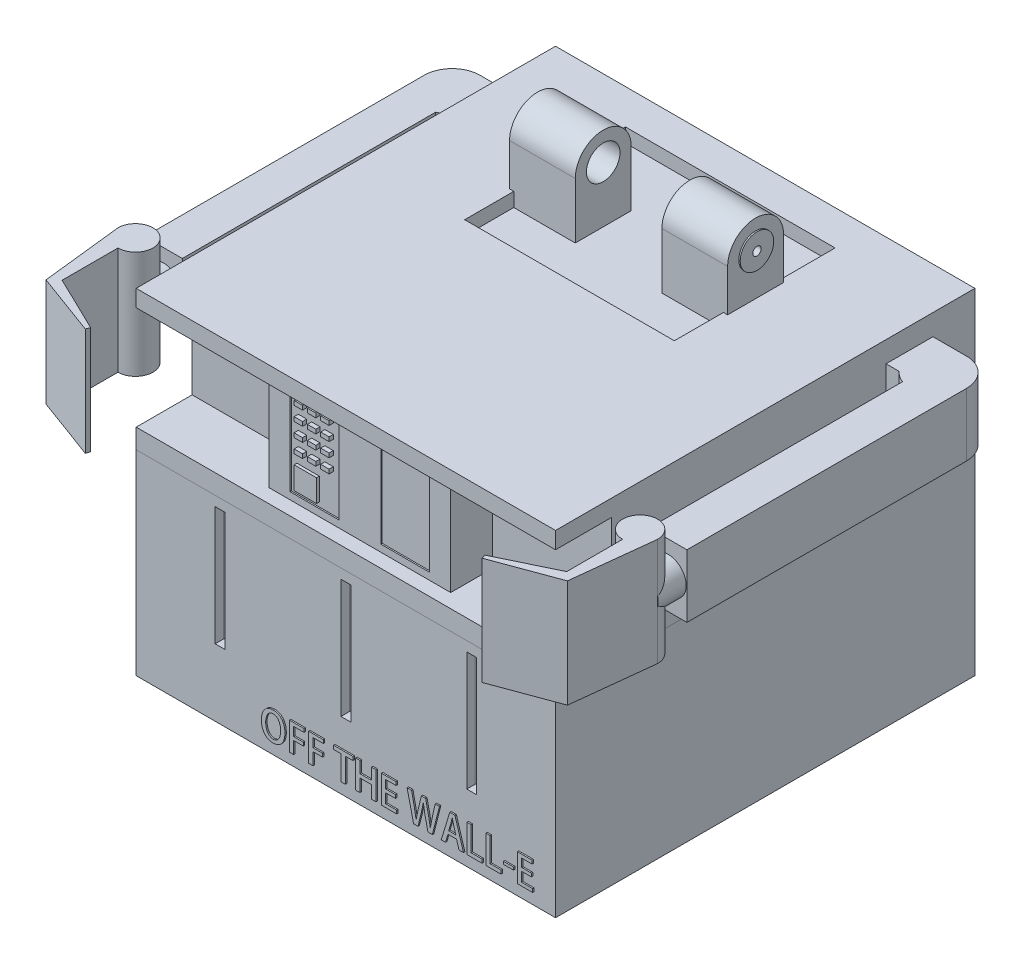
SolidWorks part; units mm, degrees
material "Polyethylene Cross-Linked"
ref_plane "Front" through (0, 0, 0) normal (0, 0, 1) x (1, 0, 0)
ref_plane "Top" through (0, 0, 0) normal (0, 1, 0) x (1, 0, 0)
ref_plane "Right" through (0, 0, 0) normal (1, 0, 0) x (0, 0, -1)
sketch "Base" plane through (0, 0, 0) normal (0, 1, 0) x (1, 0, 0)
  line L1 (-7.5, -7.5) -> (7.5, -7.5)
  line L2 (-7.5, -7.5) -> (-7.5, 7.5)
  line L3 (-7.5, 7.5) -> (7.5, 7.5)
  line L4 (7.5, -7.5) -> (7.5, 7.5)
  line L5 (-7.5, -7.5) -> (7.5, 7.5) construction
  line L6 (-7.5, 7.5) -> (7.5, -7.5) construction
  point P0 (0, 0)
  dimension "D1" = 15
  dimension "D2" = 15
extrude "Bottom base" add sketch "Base" along normal blind 7
sketch "Base2" plane through (0, 7, 0) normal (0, 1, 0) x (1, 0, 0)
  line L1 (-7.5, -7.5) -> (7.5, -7.5)
  line L2 (-7.5, -7.5) -> (-7.5, 7.5)
  line L3 (-7.5, 7.5) -> (7.5, 7.5)
  line L4 (7.5, -7.5) -> (7.5, 7.5)
  line L5 (-7.5, -7.5) -> (7.5, 7.5) construction
  line L6 (-7.5, 7.5) -> (7.5, -7.5) construction
  point P0 (0, 0)
extrude "Top base" add sketch "Base2" along normal blind 5 separate body
sketch "Sketch3" plane through (0, 0, 7.5) normal (0, 0, 1) x (1, 0, 0)
  line L7 (-7.5, 12) -> (-7.5, 7) construction
  line L8 (-7.5, 11.4) -> (7.5, 11.4)
  line L9 (-7.5, 11.4) -> (-7.5, 7.7)
  line L10 (-7.5, 7.7) -> (7.5, 7.7)
  line L11 (7.5, 11.4) -> (7.5, 7.7)
  line L12 (7.5, 12) -> (7.5, 7) construction
  line L13 (-7.5, 7) -> (7.5, 7) construction
  line L14 (-7.5, 12) -> (7.5, 12) construction
  dimension "D1" = 0.7
  dimension "D2" = 0.6
extrude "Top cut" cut sketch "Sketch3" against normal blind 2
sketch "Sketch4" plane through (0, 0, 5.5) normal (0, 0, 1) x (1, 0, 0)
  line L0 (7.5, 11.4) -> (-7.5, 11.4) construction
  line L1 (-3.25, 11.4) -> (3.25, 11.4)
  line L2 (-3.25, 11.4) -> (-3.25, 7.7)
  line L3 (-3.25, 7.7) -> (3.25, 7.7)
  line L4 (3.25, 11.4) -> (3.25, 7.7)
  line L5 (-7.5, 7.7) -> (7.5, 7.7) construction
  line L6 (-7.5, 11.4) -> (-7.5, 7.7) construction
  line L7 (7.5, 7.7) -> (7.5, 11.4) construction
  dimension "D1" = 4.25
  dimension "D2" = 4.25
extrude "Big button plate" add sketch "Sketch4" along normal blind 1.5
sketch "Sketch6" plane through (0, 0, 7) normal (0, 0, 1) x (1, 0, 0)
  line L0 (0, -55) -> (0, 55) construction
  line L1 (-2.5, 11.15) -> (-0.75, 11.15)
  line L2 (-2.5, 11.15) -> (-2.5, 7.95)
  line L3 (-2.5, 7.95) -> (-0.75, 7.95)
  line L4 (-0.75, 11.15) -> (-0.75, 7.95)
  line L5 (2.5, 7.95) -> (0.75, 7.95)
  line L6 (0.75, 11.15) -> (0.75, 7.95)
  line L7 (2.5, 11.15) -> (0.75, 11.15)
  line L8 (2.5, 11.15) -> (2.5, 7.95)
  line L9 (3.25, 11.4) -> (-3.25, 11.4) construction
  line L10 (-7.5, 7.7) -> (7.5, 7.7) construction
  line L11 (-1.775, 10.9491) -> (-1.775, 10.7991)
  line L12 (-3.25, 11.4) -> (-3.25, 7.7) construction
  line L13 (-2.5, 9.1045) -> (-0.75, 9.1045) construction
  line L14 (-1.775, 10.9491) -> (-1.475, 10.9491)
  line L15 (-2.25, 10.9491) -> (-1.95, 10.9491)
  line L16 (-2.25, 10.9491) -> (-2.25, 10.7991)
  line L17 (-2.25, 10.7991) -> (-1.95, 10.7991)
  line L18 (-1.95, 10.9491) -> (-1.95, 10.7991)
  line L19 (-1.475, 10.9491) -> (-1.475, 10.7991)
  line L20 (-1.775, 10.7991) -> (-1.475, 10.7991)
  line L21 (-1.3, 10.9491) -> (-1.3, 10.7991)
  line L22 (-1.3, 10.9491) -> (-1, 10.9491)
  line L23 (-1, 10.9491) -> (-1, 10.7991)
  line L24 (-1.3, 10.7991) -> (-1, 10.7991)
  line L25 (-2.25, 10.4491) -> (-2.25, 10.2991)
  line L26 (-2.25, 10.4491) -> (-1.95, 10.4491)
  line L27 (-1.95, 10.4491) -> (-1.95, 10.2991)
  line L28 (-2.25, 10.2991) -> (-1.95, 10.2991)
  line L29 (-1.775, 10.4491) -> (-1.775, 10.2991)
  line L30 (-1.775, 10.2991) -> (-1.475, 10.2991)
  line L31 (-1.475, 10.4491) -> (-1.475, 10.2991)
  line L32 (-1.775, 10.4491) -> (-1.475, 10.4491)
  line L33 (-1.3, 10.4491) -> (-1.3, 10.2991)
  line L34 (-1.3, 10.2991) -> (-1, 10.2991)
  line L35 (-1, 10.4491) -> (-1, 10.2991)
  line L36 (-1.3, 10.4491) -> (-1, 10.4491)
  line L37 (-2.25, 9.9491) -> (-2.25, 9.7991)
  line L38 (-2.25, 9.9491) -> (-1.95, 9.9491)
  line L39 (-1.95, 9.9491) -> (-1.95, 9.7991)
  line L40 (-2.25, 9.7991) -> (-1.95, 9.7991)
  line L41 (-1.775, 9.9491) -> (-1.775, 9.7991)
  line L42 (-1.775, 9.7991) -> (-1.475, 9.7991)
  line L43 (-1.475, 9.9491) -> (-1.475, 9.7991)
  line L44 (-1.775, 9.9491) -> (-1.475, 9.9491)
  line L45 (-1.3, 9.9491) -> (-1.3, 9.7991)
  line L46 (-1.3, 9.7991) -> (-1, 9.7991)
  line L47 (-1, 9.9491) -> (-1, 9.7991)
  line L48 (-1.3, 9.9491) -> (-1, 9.9491)
  line L49 (-2.25, 9.4491) -> (-2.25, 9.2991)
  line L50 (-2.25, 9.4491) -> (-1.95, 9.4491)
  line L51 (-1.95, 9.4491) -> (-1.95, 9.2991)
  line L52 (-2.25, 9.2991) -> (-1.95, 9.2991)
  line L53 (-1.775, 9.4491) -> (-1.775, 9.2991)
  line L54 (-1.775, 9.2991) -> (-1.475, 9.2991)
  line L55 (-1.475, 9.4491) -> (-1.475, 9.2991)
  line L56 (-1.775, 9.4491) -> (-1.475, 9.4491)
  line L57 (-1.3, 9.4491) -> (-1.3, 9.2991)
  line L58 (-1.3, 9.2991) -> (-1, 9.2991)
  line L59 (-1, 9.4491) -> (-1, 9.2991)
  line L60 (-1.3, 9.4491) -> (-1, 9.4491)
  point P32 (-1.875, 11.6241)
  dimension "D1" = 0.25
  dimension "D2" = 0.25
  dimension "D3" = 0.75
  dimension "D4" = 0.75
  dimension "D5" = 0.25
  dimension "D6" = 0.3
  dimension "D7" = 0.15
  dimension "D8" = 0.2009
  dimension "D10" = 0.25
  dimension "D9" = 3
  dimension "D11" = 4
extrude "3x4 buttons" add sketch "Sketch6" along normal blind 0.1 contours L37 L40 L39 L38 | L25 L28 L27 L26 | L16 L15 L18 L17 | L11 L20 L19 L14 | L21 L24 L23 L22 | L33 L34 L35 L36 | L29 L30 L31 L32 | L41 L42 L43 L44 | L45 L46 L47 L48 | L57 L58 L59 L60 | L53 L54 L55 L56 | L49 L52 L51 L50
sketch "Sketch9" plane through (0, 0, 7) normal (0, 0, 1) x (1, 0, 0)
  line L0 (-2.25, 9.4491) -> (-2.25, 9.2991) construction
  line L1 (-2.25, 8.9573) -> (-1.45, 8.9573)
  line L2 (-2.25, 8.9573) -> (-2.25, 8.1573)
  line L3 (-2.25, 8.1573) -> (-1.45, 8.1573)
  line L4 (-1.45, 8.9573) -> (-1.45, 8.1573)
  dimension "D1" = 0.8
  dimension "D2" = 0.8
  dimension "D3" = 0
extrude "Big square button" add sketch "Sketch9" along normal blind 0.1
extrude "phone" cut sketch "Sketch6<6>" against normal blind 0.05
sketch "Sketch6<6>" plane through (0, 0, 7) normal (0, 0, 1) x (1, 0, 0) same geometry as "Sketch6"
sketch "Sketch14" plane through (0, 0, 7.5) normal (0, 0, 1) x (1, 0, 0)
  line L0 (0, -55) -> (0, 55) construction
  line L1 (-0.175, 2.4) -> (0.175, 2.4)
  line L2 (-0.175, 2.4) -> (-0.175, 6.65)
  line L3 (-0.175, 6.65) -> (0.175, 6.65)
  line L4 (0.175, 2.4) -> (0.175, 6.65)
  line L5 (-0.175, 2.4) -> (0.175, 6.65) construction
  line L6 (-0.175, 6.65) -> (0.175, 2.4) construction
  line L7 (-7.5, 7) -> (7.5, 7) construction
  line L8 (4.325, 2.4) -> (4.325, 6.65)
  line L9 (4.325, 2.4) -> (4.675, 2.4)
  line L10 (4.675, 2.4) -> (4.675, 6.65)
  line L11 (4.325, 6.65) -> (4.675, 6.65)
  line L12 (-0.175, 2.4) -> (-0.175, 6.65)
  line L13 (-0.175, 2.4) -> (0.175, 2.4)
  line L14 (0.175, 2.4) -> (0.175, 6.65)
  line L15 (-0.175, 6.65) -> (0.175, 6.65)
  line L16 (-4.675, 2.4) -> (-4.675, 6.65)
  line L17 (-4.675, 2.4) -> (-4.325, 2.4)
  line L18 (-4.325, 2.4) -> (-4.325, 6.65)
  line L19 (-4.675, 6.65) -> (-4.325, 6.65)
  point P0 (0, 4.525)
  dimension "D1" = 0.35
  dimension "D2" = 4.25
  dimension "D3" = 0.35
  dimension "D4" = 2
  dimension "D5" = 2
extrude "3 bottom slots" cut sketch "Sketch14" against normal blind 0.35 contours L19 L16 L17 L18 | L11 L8 L9 L10 | L4 L3 L2 L1 region at (4.5, 4.525, 7.5) region at (-4.5, 4.525, 7.5)
fillet "Fillet1" radius 0.05 12 edges at (-0.175, 4.525, 7.15) (-4.675, 4.525, 7.15) (4.675, 4.525, 7.15) (4.5, 6.65, 7.15) (0.175, 4.525, 7.15) (0, 6.65, 7.15) (4.325, 4.525, 7.15) (4.5, 2.4, 7.15) (0, 2.4, 7.15) (-4.5, 2.4, 7.15) (-4.5, 6.65, 7.15) (-4.325, 4.525, 7.15)
sketch "Sketch15" plane through (0, 12, 0) normal (0, 1, 0) x (1, 0, 0)
  line L0 (0, -6.6) -> (0, 6.6) construction
  line L1 (-3.75, 0.5) -> (3.75, 0.5)
  line L2 (-3.75, 0.5) -> (-3.75, 6.25)
  line L3 (-3.75, 6.25) -> (3.75, 6.25)
  line L4 (3.75, 0.5) -> (3.75, 6.25)
  line L5 (-3.75, 0.5) -> (3.75, 6.25) construction
  line L6 (-3.75, 6.25) -> (3.75, 0.5) construction
  line L7 (7.5, 7.5) -> (-7.5, 7.5) construction
  line L8 (-6.6, 0) -> (6.6, 0) construction
  line L9 (-7.5, 7.5) -> (-7.5, -7.5) construction
  point P0 (0, 3.375)
  dimension "D1" = 1.25
  dimension "D2" = 0.5
  dimension "D3" = 3.75
extrude "Top extrude cut" cut sketch "Sketch15" against normal blind 0.5
sketch "Sketch18" plane through (-3.75, 0, 0) normal (1, 0, 0) x (0, 0, -1)
  line L0 (2.2556, 11.5) -> (4.2556, 11.5)
  line L1 (6.25, 11.5) -> (0.5, 11.5) construction
  line L3 (2.2556, 11.5) -> (2.2556, 13.5)
  line L4 (4.2556, 11.5) -> (4.2556, 13.5)
  arc A0 (2.2556, 13.5) -> (4.2556, 13.5) centre (3.2556, 13.5) cw
  circle A1 centre (3.2556, 13.5) radius 0.6
  circle A2 centre (3.2556, 13.5) radius 0.15
  line M6 (6.25, 12) -> (0.5, 12)
  line M8 (0.5, 11.5) -> (6.25, 11.5)
  dimension "D5" = 0.3
  dimension "D1" = 2
  dimension "D2" = 2
  dimension "D3" = 2
  dimension "D4" = 0.4
sketch "Sketch19" plane through (3.75, 0, 0) normal (-1, 0, 0) x (0, 0, 1)
  line L0 (-4.2556, 13.5) -> (-4.2556, 11.5)
  line L1 (-4.2556, 11.5) -> (-2.2556, 11.5)
  line L2 (-2.2556, 11.5) -> (-2.2556, 13.5)
  arc A0 (-4.2556, 13.5) -> (-2.2556, 13.5) centre (-3.2556, 13.5) cw
  circle A1 centre (-3.2556, 13.5) radius 0.6
  circle A2 centre (-3.2556, 13.5) radius 0.15
  line M1 (-0.5, 12) -> (-6.25, 12)
  line M3 (-6.25, 11.5) -> (-0.5, 11.5)
extrude "Right head holder 1" add sketch "Sketch19" along normal blind 2.2 and the other way blind 0.15 contours A0 L0 L2 A1 M1 | L2 L0 M3 M1 region at (3.75, 14.468, -3.2556) region at (3.75, 11.75, -3.2556)
extrude "Right head holder 2" add sketch "Sketch19<3>" against normal blind 0.2 and the other way blind 0.35 contours A1 A2 region at (3.75, 13.5, -3.8386)
sketch "Sketch19<3>" plane through (3.75, 0, 0) normal (-1, 0, 0) x (0, 0, 1) same geometry as "Sketch19"
extrude "Left head holder 1" add sketch "Sketch18" along normal blind 2.2 and the other way blind 0.15 contours L4 L3 M8 M6 | A0 L3 L4 A1 M6 region at (-3.75, 11.75, -3.2556) region at (-3.75, 12.75, -2.2876)
extrude "Left head holder 2" add sketch "Sketch18<3>" along normal blind 0.35 and the other way blind 0.2 contours A1 A2 region at (-3.75, 13.5, -2.6726)
sketch "Sketch18<3>" plane through (-3.75, 0, 0) normal (1, 0, 0) x (0, 0, -1) same geometry as "Sketch18"
ref_plane "Plane9" through (0, 9, 0) normal (0, 1, 0) x (1, 0, 0)
sketch "Sketch21" plane through (0, 9, 0) normal (0, 1, 0) x (1, 0, 0)
  line L0 (7.9641, 4.3229) -> (7.5, 4.3229)
  line L1 (7.5, 6) -> (7.5, 4.3229)
  line L5 (0, -6.6) -> (0, 6.6) construction
  line L12 (8.7, 6) -> (7.5, 6)
  line L17 (9.7, 5) -> (8.35, 5)
  line L18 (9.7, 5) -> (9.7, -5)
  line L19 (9.7, -5) -> (8.35, -5)
  line L20 (8.35, 5) -> (8.35, -5)
  line L21 (7.5, -7.5) -> (7.5, 7.5) construction
  line L22 (-8.7, 6) -> (-7.5, 6)
  line L23 (-7.5, 6) -> (-7.5, 4.3229)
  line L24 (-7.9641, 4.3229) -> (-7.5, 4.3229)
  line L25 (-9.7, -5) -> (-8.35, -5)
  line L26 (-8.35, 5) -> (-8.35, -5)
  line L27 (-9.7, 5) -> (-8.35, 5)
  line L28 (-9.7, 5) -> (-9.7, -5)
  circle A6 centre (8.7, 5) radius 1
  arc A7 (8.7, 6) -> (7.9641, 4.3229) centre (8.7, 5) ccw
  arc A8 (-8.7, 6) -> (-7.9641, 4.3229) centre (-8.7, 5) cw
  circle A9 centre (-8.7, 5) radius 1
  point P1 (8.7, 5)
  point P19 (7.9641, 4.3229)
  dimension "D1" = 2
  dimension "D2" = 1.35
  dimension "D3" = 10
  dimension "D4" = 1.2
extrude "arms" add sketch "Sketch21" along normal blind 2.25 contours A6 L12 L1 L0 | L17 A6 L20 | L20 A6 L17 | A6 L20 L19 L18 | L22 A8 L24 L23 | A9 L27 L26 A8 | A9 L26 L27 | L26 A9 L28 L25 region at (7.7309, 9, -5.3169) region at (8.5639, 9, -5.2489) region at (9.0325, 9, 0.4154) region at (8.9429, 9, -4.5557) region at (-7.7309, 9, -5.3169) region at (-8.5639, 9, -5.2489) region at (-9.0325, 9, 0.4154) region at (-8.9429, 9, -4.5557)
sketch "Sketch25" plane through (0, 11.25, 0) normal (0, 1, 0) x (1, 0, 0)
  line L0 (9.7, 5) -> (9.7, -5) construction
  line L1 (9.7, -5) -> (8.35, -5) construction
  line L2 (9.65, -6) -> (9.326, -8.9)
  line L3 (9.025, -8.625) -> (9.025, -6.625)
  line L4 (9.326, -8.9) -> (7.1001, -9.7215)
  line L5 (7.1001, -9.7215) -> (7.0482, -9.5808)
  line L6 (7.0482, -9.5808) -> (9.025, -8.625)
  line L7 (0, -6.6) -> (0, 6.6) construction
  line L8 (-7.1001, -9.7215) -> (-7.0482, -9.5808)
  line L9 (-7.0482, -9.5808) -> (-9.025, -8.625)
  line L10 (-9.326, -8.9) -> (-7.1001, -9.7215)
  line L11 (-9.025, -8.625) -> (-9.025, -6.625)
  line L12 (-9.65, -6) -> (-9.326, -8.9)
  circle A0 centre (9.025, -6) radius 0.625
  arc A1 (9.025, -6.625) -> (9.65, -6) centre (9.025, -6) ccw
  circle A2 centre (-9.025, -6) radius 0.625
  dimension "D3" = 1.25
  dimension "D1" = 0.675
  dimension "D2" = 1
  dimension "D4" = 2
  dimension "D5" = 2.9
  dimension "D6" = 0.15
extrude "claws" add sketch "Sketch25" along normal blind 0.8 and the other way blind 3.05 separate body contours A2 L12 | L11 A2 L12 L10 L8 L9 | A0 L2 | A0 L3 L6 L5 L4 L2 region at (9.0248, 11.25, 6) region at (9.4364, 11.25, 7.5141) region at (-8.1978, 11.25, 9.2693) region at (-9.0248, 11.25, 6)
sketch "Sketch26" plane through (0, 0, 5) normal (0, 0, 1) x (1, 0, 0)
  line L0 (9.7, 11.25) -> (9.7, 9) construction
  line L1 (9.7, 11.25) -> (8.35, 11.25) construction
  line L2 (0, -6.6) -> (0, 6.6) construction
  circle A0 centre (9.025, 10.125) radius 0.65
  circle A1 centre (-9.025, 10.125) radius 0.65
  dimension "D3" = 1.3
  dimension "D1" = 0.675
  dimension "D2" = 1.125
extrude "circle to attach arms and claws" add sketch "Sketch26" along normal blind 1 contours A1 | A0 region at (-9.025, 10.125, 5)
sketch "Sketch28" plane through (0, 0, 7.5) normal (0, 0, 1) x (1, 0, 0)
  text T0 "OFF THE WALL-E" font "@Adobe Heiti Std R" height 1
  point P12 (-3, 0.4)
extrude "Boss-Extrude26" add sketch "Sketch28" along normal blind 0.05
sketch "Sketch33" plane through (0, 0, 0) normal (0, -1, 0) x (1, 0, 0)
  line L1 (-7.0571, 0.7429) -> (-5.7714, 0.7429)
  line L2 (-7.0571, 0.7429) -> (-7.0571, -0.5429)
  line L3 (-7.0571, -0.5429) -> (-5.7714, -0.5429)
  line L4 (-5.7714, 0.7429) -> (-5.7714, -0.5429)
  line L5 (-7.0571, 0.7429) -> (-5.7714, -0.5429) construction
  line L6 (-7.0571, -0.5429) -> (-5.7714, 0.7429) construction
  line L7 (6.6, 0) -> (-6.6, 0) construction
  line L8 (-7.5, -7.5) -> (-7.5, 7.5) construction
  line L9 (0, -6.6) -> (0, 6.6) construction
  line L10 (7.0571, -0.5429) -> (5.7714, 0.7429) construction
  line L11 (7.0571, 0.7429) -> (5.7714, -0.5429) construction
  line L12 (5.7714, 0.7429) -> (5.7714, -0.5429)
  line L13 (7.0571, -0.5429) -> (5.7714, -0.5429)
  line L14 (7.0571, 0.7429) -> (7.0571, -0.5429)
  line L15 (7.0571, 0.7429) -> (5.7714, 0.7429)
  point P0 (-6.4143, 0.1)
  point P15 (6.4143, 0.1)
  dimension "D1" = 1.2857
  dimension "D2" = 1.2857
  dimension "D3" = 0.1
  dimension "D4" = 1.0857
extrude "Cut-Extrude1" cut sketch "Sketch33" against normal blind 2.8929
scale "Scale1" bodies to scale 109 128 135 scale about origin uniform scaling yes scale factor 1.4
equation "\"D2@Sketch4\"=\"D1@Sketch4\""
equation "\"D4@Sketch6\"=\"D3@Sketch6\""
equation "\"D3@Sketch18\"=\"D2@Sketch18\""
